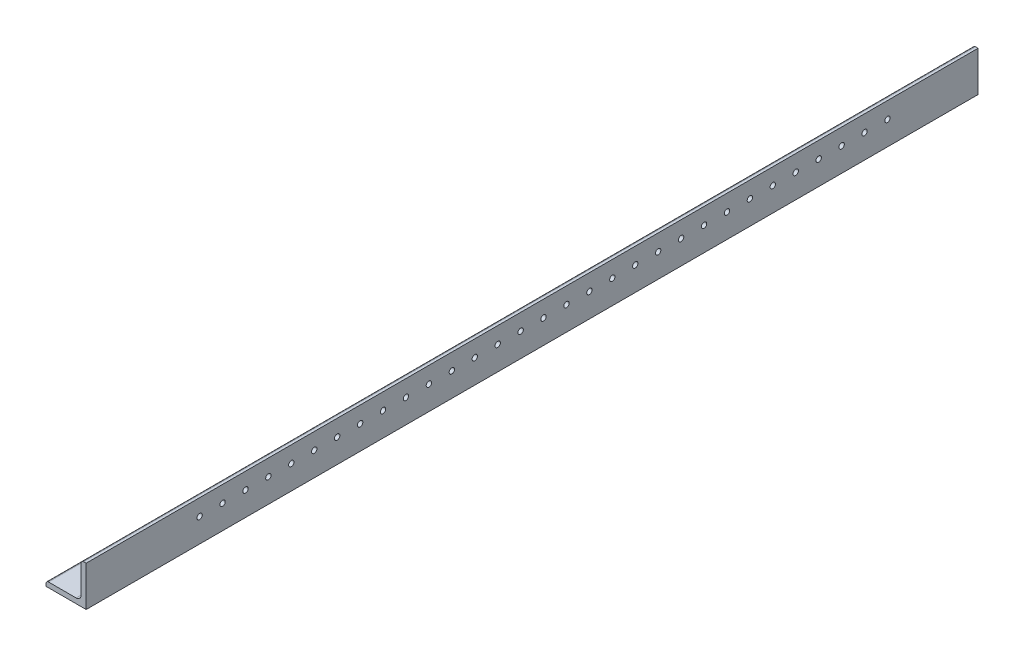
SolidWorks part; units mm, degrees
ref_plane "Front Plane" through (0, 0, 0) normal (0, 0, 1) x (1, 0, 0)
ref_plane "Top Plane" through (0, 0, 0) normal (0, 1, 0) x (1, 0, 0)
ref_plane "Right Plane" through (0, 0, 0) normal (1, 0, 0) x (0, 0, -1)
sketch "Sketch0" plane through (0, 0, 0) normal (0, 0, 1) x (1, 0, 0)
  line L0 (-12.7, -12.7) -> (12.7, -12.7)
  line L1 (12.7, -12.7) -> (12.7, 12.7)
  line L2 (12.7, 0) -> (0, 0) construction
  line L3 (0, 0) -> (0, -12.7) construction
  line L4 (9.525, -6.35) -> (9.525, 12.7) construction
  line L5 (6.35, -9.525) -> (-12.7, -9.525) construction
  arc A0 (9.525, -6.35) -> (6.35, -9.525) centre (6.35, -6.35) cw
  point P3 (8.5951, -8.5951)
  dimension "Inside Corner Radius" = 3.175
  dimension "Outside Height" = 25.4
  dimension "Inside Height" = 22.225
  dimension "Inside Width" = 22.225
  dimension "Wall Thickness" = 3.175
  dimension "D1" = 3.175
  dimension "Outside Width" = 25.4
sketch "Sketch1" plane through (0, 0, 0) normal (1, 0, 0) x (0, 0, -1)
  line L0 (609.6, 0) -> (-609.6, 0)
  point P4 (0, 0)
  dimension "Length" = 1219.2
sketch "Sketch2" plane through (0, 0, 0) normal (0, 0, 1) x (1, 0, 0)
  line L0 (-12.7, -12.7) -> (12.7, -12.7)
  line L1 (12.7, -12.7) -> (12.7, 12.7)
  line L2 (12.7, 12.7) -> (9.525, 12.7) construction
  line L3 (9.525, 11.1125) -> (9.525, -6.35)
  line L4 (6.35, -9.525) -> (-11.1125, -9.525)
  line L5 (-12.7, -12.7) -> (-12.7, -9.525) construction
  line L6 (11.1125, 12.7) -> (12.7, 12.7)
  line L7 (-12.7, -11.1125) -> (-12.7, -12.7)
  line L8 (12.7, 0) -> (0, 0) construction
  line L9 (0, 0) -> (0, -12.7) construction
  arc A0 (9.525, 11.1125) -> (11.1125, 12.7) centre (11.1125, 11.1125) cw
  arc A1 (-12.7, -11.1125) -> (-11.1125, -9.525) centre (-11.1125, -11.1125) cw
  arc A2 (9.525, -6.35) -> (6.35, -9.525) centre (6.35, -6.35) cw
  dimension "Inside Radius" = 3.175
  dimension "Height" = 25.4
  dimension "Width" = 25.4
  dimension "Thickness" = 3.175
extrude "Boss-Extrude1" add sketch "Sketch2" along normal mid plane 1219.2
sketch "Break Locations" plane through (0, 0, 0) normal (1, 0, 0) x (0, 0, -1)
  line L0 (-583.692, 0) -> (583.692, 0)
  line L1 (-609.6, -12.7) -> (-609.6, 12.7) construction
  line L2 (609.6, -12.7) -> (609.6, 12.7) construction
  point P0 (-588.01, 0)
  point P1 (588.01, 0)
  point P10 (0, 0)
  point P11 (583.692, 0)
  point P13 (-583.692, 0)
  dimension "D1" = 21.59
  dimension "D2" = 21.59
  dimension "D3" = 25.908
sketch "Sketch3" plane through (12.7, 0, 0) normal (1, 0, 0) x (0, 0, -1)
  line L0 (-609.6, -12.7) -> (609.6, -12.7) construction
  line L1 (609.6, 12.7) -> (-45.6, 12.7)
  line L2 (609.6, 12.7) -> (609.6, -12.7)
  line L3 (609.6, -12.7) -> (-45.6, -12.7)
  line L4 (-45.6, 12.7) -> (-45.6, -12.7)
  line L5 (-609.6, -12.7) -> (-609.6, 12.7) construction
  dimension "D1" = 564
extrude "Cut-Extrude2" cut sketch "Sketch3" against normal blind 30.48
sketch "Sketch4" plane through (0, -9.525, 0) normal (0, 1, 0) x (1, 0, 0)
  line L0 (-11.1125, -92.4325) -> (6.35, -92.4325) construction
  line L1 (-11.1125, -609.6) -> (-11.1125, -45.6) construction
  line L2 (3.9675, -92.4325) -> (-8.7325, -92.4325) construction
  line L3 (6.35, -609.6) -> (6.35, -45.6) construction
  line L4 (-2.3812, -92.4325) -> (-2.3812, -562.7675) construction
  line L5 (-8.7325, -562.7675) -> (3.9675, -562.7675) construction
  line L6 (-11.1125, -562.7675) -> (6.35, -562.7675) construction
  line L7 (-2.3812, -552.35) -> (-2.3812, -562.7675)
  line L8 (-2.3813, -102.85) -> (-2.3812, -92.4325)
  circle A0 centre (-2.3812, -552.35) radius 1.7
  circle A1 centre (-2.3813, -537.85) radius 1.7
  circle A2 centre (-2.3813, -523.35) radius 1.7
  circle A3 centre (-2.3813, -508.85) radius 1.7
  circle A4 centre (-2.3813, -494.35) radius 1.7
  circle A5 centre (-2.3813, -479.85) radius 1.7
  circle A6 centre (-2.3813, -465.35) radius 1.7
  circle A7 centre (-2.3813, -450.85) radius 1.7
  circle A8 centre (-2.3813, -436.35) radius 1.7
  circle A9 centre (-2.3813, -421.85) radius 1.7
  circle A10 centre (-2.3813, -407.35) radius 1.7
  circle A11 centre (-2.3813, -392.85) radius 1.7
  circle A12 centre (-2.3813, -378.35) radius 1.7
  circle A13 centre (-2.3813, -363.85) radius 1.7
  circle A14 centre (-2.3813, -349.35) radius 1.7
  circle A15 centre (-2.3813, -334.85) radius 1.7
  circle A16 centre (-2.3813, -320.35) radius 1.7
  circle A17 centre (-2.3813, -305.85) radius 1.7
  circle A18 centre (-2.3813, -291.35) radius 1.7
  circle A19 centre (-2.3813, -276.85) radius 1.7
  circle A20 centre (-2.3813, -262.35) radius 1.7
  circle A21 centre (-2.3813, -247.85) radius 1.7
  circle A22 centre (-2.3813, -233.35) radius 1.7
  circle A23 centre (-2.3813, -218.85) radius 1.7
  circle A24 centre (-2.3813, -204.35) radius 1.7
  circle A25 centre (-2.3813, -189.85) radius 1.7
  circle A26 centre (-2.3813, -175.35) radius 1.7
  circle A27 centre (-2.3813, -160.85) radius 1.7
  circle A28 centre (-2.3813, -146.35) radius 1.7
  circle A29 centre (-2.3813, -131.85) radius 1.7
  circle A30 centre (-2.3813, -117.35) radius 1.7
  circle A31 centre (-2.3813, -102.85) radius 1.7
  point P16 (-2.3812, -546.31)
  point P17 (-2.3812, -100.4375)
  dimension "D1" = 3.4
  dimension "D3" = 14.5
  dimension "D2" = 32
extrude "Cut-Extrude4" cut sketch "Sketch4" against normal through all contours A0 | A1 | A2 | A3 | A4 | A5 | A6 | A7 | A8 | A9 | A10 | A11 | A12 | A13 | A14 | A15 | A16 | A17 | A18 | A19 | A20 | A21 | A22 | A23 | A24 | A25 | A26 | A27 | A28 | A29 | A30 | A31
sketch "Sketch7" plane through (9.525, 0, 0) normal (-1, 0, 0) x (0, 0, 1)
  line L0 (92.4325, 11.1125) -> (92.4325, -6.35) construction
  line L2 (609.6, 11.1125) -> (45.6, 11.1125) construction
  line L3 (92.4325, -3.9675) -> (92.4325, 8.7325) construction
  line L4 (609.6, -6.35) -> (45.6, -6.35) construction
  line L5 (92.4325, 2.3812) -> (562.7675, 2.3812) construction
  line L6 (562.7675, -3.9675) -> (562.7675, 8.7325) construction
  line L7 (102.85, 2.3812) -> (92.4325, 2.3812)
  line L8 (552.35, 2.3812) -> (562.7675, 2.3812)
  circle A0 centre (552.35, 2.3812) radius 1.7
  circle A1 centre (537.85, 2.3812) radius 1.7
  circle A2 centre (523.35, 2.3812) radius 1.7
  circle A3 centre (508.85, 2.3812) radius 1.7
  circle A4 centre (494.35, 2.3812) radius 1.7
  circle A5 centre (479.85, 2.3812) radius 1.7
  circle A6 centre (465.35, 2.3812) radius 1.7
  circle A7 centre (450.85, 2.3812) radius 1.7
  circle A8 centre (436.35, 2.3812) radius 1.7
  circle A9 centre (421.85, 2.3812) radius 1.7
  circle A10 centre (407.35, 2.3812) radius 1.7
  circle A11 centre (392.85, 2.3812) radius 1.7
  circle A12 centre (378.35, 2.3812) radius 1.7
  circle A13 centre (363.85, 2.3812) radius 1.7
  circle A14 centre (349.35, 2.3812) radius 1.7
  circle A15 centre (334.85, 2.3812) radius 1.7
  circle A16 centre (320.35, 2.3812) radius 1.7
  circle A17 centre (305.85, 2.3812) radius 1.7
  circle A18 centre (291.35, 2.3812) radius 1.7
  circle A19 centre (276.85, 2.3812) radius 1.7
  circle A20 centre (262.35, 2.3812) radius 1.7
  circle A21 centre (247.85, 2.3812) radius 1.7
  circle A22 centre (233.35, 2.3812) radius 1.7
  circle A23 centre (218.85, 2.3812) radius 1.7
  circle A24 centre (204.35, 2.3812) radius 1.7
  circle A25 centre (189.85, 2.3812) radius 1.7
  circle A26 centre (175.35, 2.3812) radius 1.7
  circle A27 centre (160.85, 2.3812) radius 1.7
  circle A28 centre (146.35, 2.3812) radius 1.7
  circle A29 centre (131.85, 2.3812) radius 1.7
  circle A30 centre (117.35, 2.3812) radius 1.7
  circle A31 centre (102.85, 2.3812) radius 1.7
  dimension "D1" = 3.4
  dimension "D3" = 14.5
  dimension "D2" = 32
extrude "Cut-Extrude6" cut sketch "Sketch7" against normal through all contours A1 | A2 | A3 | A4 | A5 | A6 | A7 | A8 | A9 | A10 | A11 | A12 | A13 | A14 | A15 | A16 | A17 | A18 | A19 | A20 | A21 | A22 | A23 | A24 | A25 | A26 | A27 | A28 | A29 | A30 | A31 | A9 | A20 | A24 | A28 region at (9.525, 2.3812, 537.85) region at (9.525, 2.3812, 523.35) region at (9.525, 2.3812, 508.85) region at (9.525, 2.3812, 494.35) region at (9.525, 2.3812, 479.85) region at (9.525, 2.3812, 465.35) region at (9.525, 2.3812, 450.85) region at (9.525, 2.3812, 436.35) region at (9.525, 2.3812, 421.85) region at (9.525, 2.3812, 407.35) region at (9.525, 2.3812, 392.85) region at (9.525, 2.3812, 378.35) region at (9.525, 2.3812, 363.85) region at (9.525, 2.3812, 349.35) region at (9.525, 2.3812, 334.85) region at (9.525, 2.3812, 320.35) region at (9.525, 2.3812, 305.85) region at (9.525, 2.3812, 291.35) region at (9.525, 2.3812, 276.85) region at (9.525, 2.3812, 262.35) region at (9.525, 2.3812, 247.85) region at (9.525, 2.3812, 233.35) region at (9.525, 2.3812, 218.85) region at (9.525, 2.3812, 204.35) region at (9.525, 2.3812, 189.85) region at (9.525, 2.3812, 175.35) region at (9.525, 2.3812, 160.85) region at (9.525, 2.3812, 146.35) region at (9.525, 2.3812, 131.85) region at (9.525, 2.3812, 117.35) region at (9.525, 0.7293, 102.85)
equation "\"D1@Break Locations\" = .85 * \"Height@Sketch2\""
equation "\"D2@Break Locations\"=\"D1@Break Locations\""
equation "\"Thickness@Sketch2\" = \"Wall Thickness@Sketch0\""
equation "\"Height@Sketch2\" = \"Outside Height@Sketch0\""
equation "\"Width@Sketch2\" = \"Outside Width@Sketch0\""
equation "\"Inside Radius@Sketch2\" = \"Inside Corner Radius@Sketch0\""
equation "\"Length@Boss-Extrude1\" = \"Length@Sketch1\""
equation "\"D3@Break Locations\"=\"D2@Break Locations\"*1.2"
equation "\"D1@Sketch0\"=\"Wall Thickness@Sketch0\""
